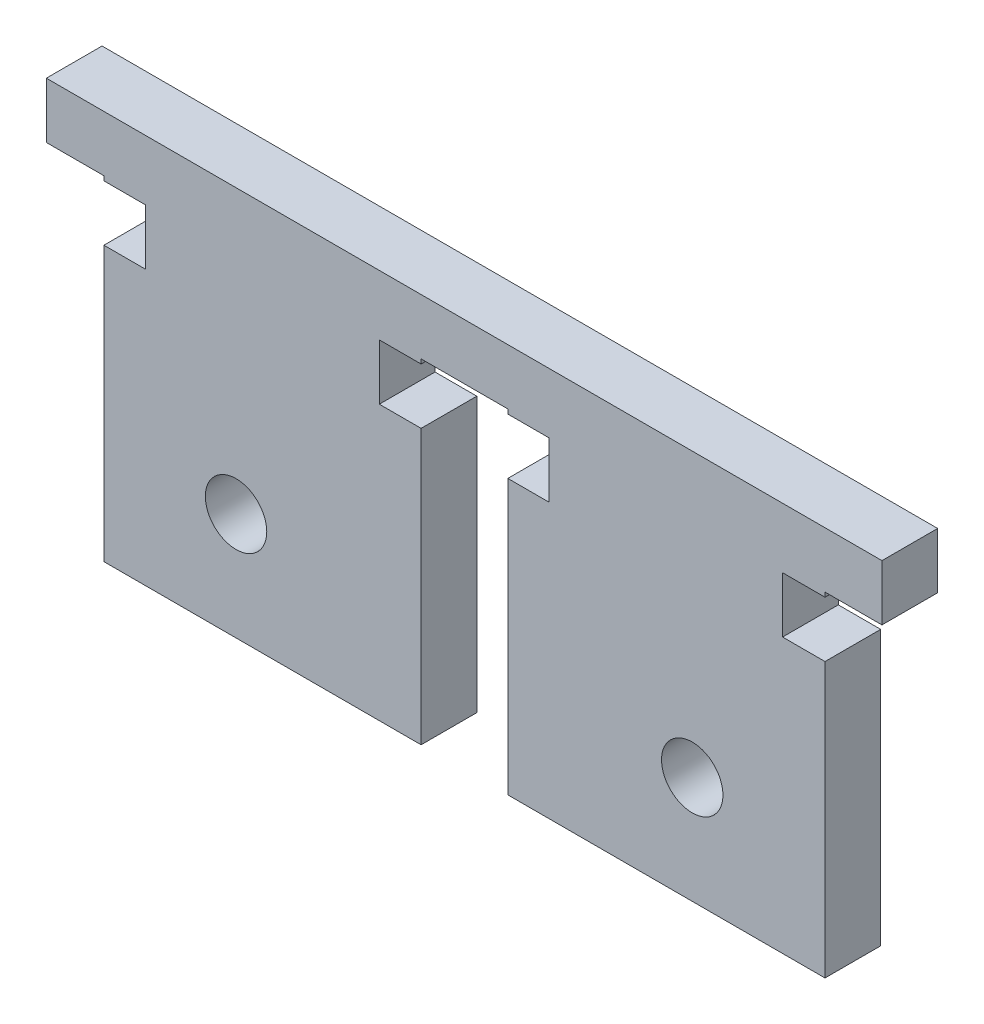
SolidWorks part; units mm, degrees
material "AISI 4130 Steel, annealed at 865C"
ref_plane "X-Y Datum" through (0, 0, 0) normal (0, 0, 1) x (1, 0, 0)
ref_plane "X-Z Datum" through (0, 0, 0) normal (0, 1, 0) x (1, 0, 0)
ref_plane "Y-Z Datum" through (0, 0, 0) normal (1, 0, 0) x (0, 0, -1)
sketch "Sketch3" plane through (0, 0, 0) normal (0, 0, 1) x (1, 0, 0)
  line L1 (-47.625, -30.48) -> (47.625, -30.48)
  line L2 (-47.625, -30.48) -> (-47.625, 30.48)
  line L3 (-47.625, 30.48) -> (47.625, 30.48)
  line L4 (47.625, -30.48) -> (47.625, 30.48)
  line L5 (-47.625, -30.48) -> (47.625, 30.48) construction
  line L6 (-47.625, 30.48) -> (47.625, -30.48) construction
  point P0 (0, 0)
  dimension "D1" = 95.25
  dimension "D2" = 60.96
extrude "Boss-Extrude1" add sketch "Sketch3" along normal blind 6.35
sketch "Sketch4" plane through (0, 0, 6.35) normal (0, 0, 1) x (1, 0, 0)
  line L0 (-47.625, 15.24) -> (-41.0616, 15.24)
  line L1 (-47.625, 30.48) -> (-47.625, -30.48) construction
  line L2 (-41.0616, 15.24) -> (-4.5491, 15.24)
  line L3 (-4.5491, 15.24) -> (4.6203, 15.24)
  line L4 (4.6203, 15.24) -> (41.1328, 15.24)
  line L5 (41.1328, 15.24) -> (47.625, 15.24)
  line L6 (47.625, -30.48) -> (47.625, 30.48) construction
  line L7 (0.0356, 15.24) -> (0.0356, -30.48) construction
  line L8 (-41.0616, 15.24) -> (-47.625, 15.24)
  line L9 (-41.0616, 15.24) -> (-41.0616, -30.48)
  line L10 (-41.0616, -30.48) -> (-47.625, -30.48)
  line L11 (-47.625, 15.24) -> (-47.625, -30.48)
  line L12 (-47.625, -30.48) -> (47.625, -30.48) construction
  line L13 (-1.5519, -16.0071) -> (1.6231, -16.0071)
  line L14 (-1.5519, -16.0071) -> (-1.5519, 0.7671)
  line L17 (-4.5491, 15.24) -> (4.6203, 15.24)
  line L19 (-4.9063, -30.48) -> (4.9774, -30.48)
  line L20 (-4.9063, -30.48) -> (-4.9063, 15.24)
  line L25 (-4.9063, 15.24) -> (4.9774, 15.24)
  line L26 (4.9774, -30.48) -> (4.9774, 15.24)
  line L27 (41.1328, 15.24) -> (47.625, 15.24)
  line L28 (41.1328, 15.24) -> (41.1328, -30.48)
  line L29 (41.1328, -30.48) -> (47.625, -30.48)
  line L31 (-4.9063, -30.48) -> (4.9774, 15.24) construction
  line L32 (-4.9063, 15.24) -> (4.9774, -30.48) construction
  line L33 (-1.5519, 0.7671) -> (1.6231, 0.7671)
  line L34 (1.6231, -16.0071) -> (1.6231, 0.7671)
  line L35 (-1.5519, -16.0071) -> (1.6231, 0.7671) construction
  line L36 (-1.5519, 0.7671) -> (1.6231, -16.0071) construction
  point P15 (0.0356, -7.62)
  point P20 (0.0356, -7.62)
  line M5 (47.625, -30.48) -> (47.625, 30.48)
  line M7 (-47.625, 30.48) -> (-47.625, -30.48)
  line M8 (-47.625, -30.48) -> (47.625, -30.48)
  dimension "D1" = 6.5634
  dimension "D2" = 36.5125
  dimension "D3" = 6.4922
  dimension "D4" = 36.5125
  dimension "D5" = 9.8837
  dimension "D6" = 45.72
  dimension "D7" = 3.175
  dimension "D9" = 45.72
extrude "Cut-Extrude1" cut sketch "Sketch4" against normal blind 6.35 contours L9 L0 M7 M8 | L5 L28 M8 M5 | L19 L26 L4 L3 L2 L20 L34 L13 L14 L33 | L13 L34 L33 L14 region at (-44.3433, -7.62, 6.35) region at (-4.7277, 14.7722, 6.35) region at (44.3789, -7.62, 6.35) region at (0.0356, -7.62, 6.35)
sketch "Sketch5" plane through (0, 0, 6.35) normal (0, 0, 1) x (1, 0, 0)
  line L0 (-41.0616, 8.382) -> (-36.2991, 8.382) construction
  line L9 (-22.984, -30.48) -> (-22.984, 30.48) construction
  line L10 (-41.0616, 8.382) -> (-36.2991, 8.382)
  line L12 (-41.0616, 14.732) -> (-36.2991, 14.732)
  line L13 (-36.2991, 8.382) -> (-36.2991, 14.732)
  line L14 (-41.0616, -30.48) -> (-4.9063, -30.48) construction
  line L15 (47.625, 30.48) -> (-47.625, 30.48) construction
  line L16 (-41.0616, 14.732) -> (-47.6562, 14.732)
  line L17 (-4.9063, 8.382) -> (-9.6688, 8.382)
  line L18 (-4.9063, 8.382) -> (-4.9063, 14.732)
  line L19 (-4.9063, 14.732) -> (-9.6688, 14.732)
  line L20 (-9.6688, 8.382) -> (-9.6688, 14.732)
  line L22 (-41.0616, 8.382) -> (-47.6562, 8.382)
  line L23 (-47.6562, 14.732) -> (-47.6562, 8.382)
  line L24 (-41.0616, 15.24) -> (-41.0616, -30.48) construction
  line M5 (-41.0616, 15.24) -> (-41.0616, -30.48)
  line M15 (-47.625, 30.48) -> (-47.625, 15.24)
  line M16 (-47.625, 15.24) -> (-41.0616, 15.24)
  dimension "D1" = 6.35
  dimension "D2" = 4.7625
  dimension "D3" = 15.748
extrude "Cut-Extrude2" cut sketch "Sketch5" against normal blind 6.35 contours L10 L13 L12 | L20 L17 L18 L19 | L16 L23 L22 M5 M16 M15 region at (-38.6804, 11.557, 6.35) region at (-44.3589, 11.557, 6.35) region at (-7.2875, 11.557, 6.35)
mirror "Mirror1" about plane through (0, 0, 0) normal (1, 0, 0) of "Cut-Extrude2"
sketch "Sketch8" [suppressed] plane through (0, 15.24, 0) normal (0, -1, 0) x (1, 0, 0)
  line L0 (-9.525, 3.175) -> (9.525, 3.175) construction
  line L1 (-9.525, 0) -> (-9.525, 6.35) construction
  line L2 (9.525, 0) -> (9.525, 6.35) construction
  line L3 (-4.7625, 6.35) -> (4.7625, 6.35) construction
  line L4 (-4.7625, 0) -> (4.7625, 0)
  line L5 (-4.7625, 0) -> (-4.7625, 6.35)
  line L6 (-4.7625, 6.35) -> (4.7625, 6.35)
  line L7 (4.7625, 0) -> (4.7625, 6.35)
  line L8 (-4.7625, 0) -> (4.7625, 6.35) construction
  line L9 (-4.7625, 6.35) -> (4.7625, 0) construction
  point P6 (0, 3.175)
  line M3 (-4.7625, 0) -> (4.7625, 0)
  dimension "D1" = 4.7625
extrude "Cut-Extrude3" [suppressed] cut sketch "Sketch8" against normal blind 1.5875 contours L7 L0 L5 M3
sketch "Sketch9" plane through (0, 30.48, 0) normal (0, 1, 0) x (1, 0, 0)
  line L1 (-47.625, 0) -> (47.625, 0)
  line L2 (-47.625, 0) -> (-47.625, -6.35)
  line L3 (-47.625, -6.35) -> (47.625, -6.35)
  line L4 (47.625, 0) -> (47.625, -6.35)
extrude "Cut-Extrude6" cut sketch "Sketch9" against normal blind 8.89
sketch "Sketch10" plane through (0, 0, 6.35) normal (0, 0, 1) x (1, 0, 0)
  line L0 (0, 0) -> (0, -30.2463) construction
  line L1 (-26, -10.6279) -> (26, -10.6279) construction
  circle A1 centre (-26, -10.6279) radius 3.3015
  circle A3 centre (26, -10.6279) radius 3.3015
  point P2 (26, -10.6279)
  point P10 (-26, -10.6279)
  point P21 (-26, -10.6279)
  point P23 (26, -10.6279)
  dimension "D2" = 6.603
  dimension "D1" = 52
sketch "Sketch11" plane through (0, -30.48, 0) normal (0, -1, 0) x (1, 0, 0)
  line L1 (-41.0616, 6.35) -> (41.1328, 6.35)
  line L2 (-41.0616, 6.35) -> (-41.0616, 0)
  line L3 (-41.0616, 0) -> (41.1328, 0)
  line L4 (41.1328, 6.35) -> (41.1328, 0)
extrude "Cut-Extrude9" cut sketch "Sketch11" against normal blind 7.62
hole_wizard "M6 Clearance Hole2" positions "Sketch10" profile "Sketch12" hole size "M6" standard "ANSI Metric" end condition through all
sketch "Sketch12" plane through (26, -10.6279, 6.35) normal (1, 0, 0) x (0, -1, 0)
  line L0 (0, 0) -> (0, 6.35)
  line L1 (0, 6.35) -> (3.5, 6.35)
  line L2 (3.5, 6.35) -> (3.5, 0)
  line L5 (3.5, 0) -> (0, 0)
  line L11 (0, -6.35) -> (0, 107.95) construction
  dimension "Thru Hole Dia." = 7
  dimension "Thru Hole Depth" = 6.35
